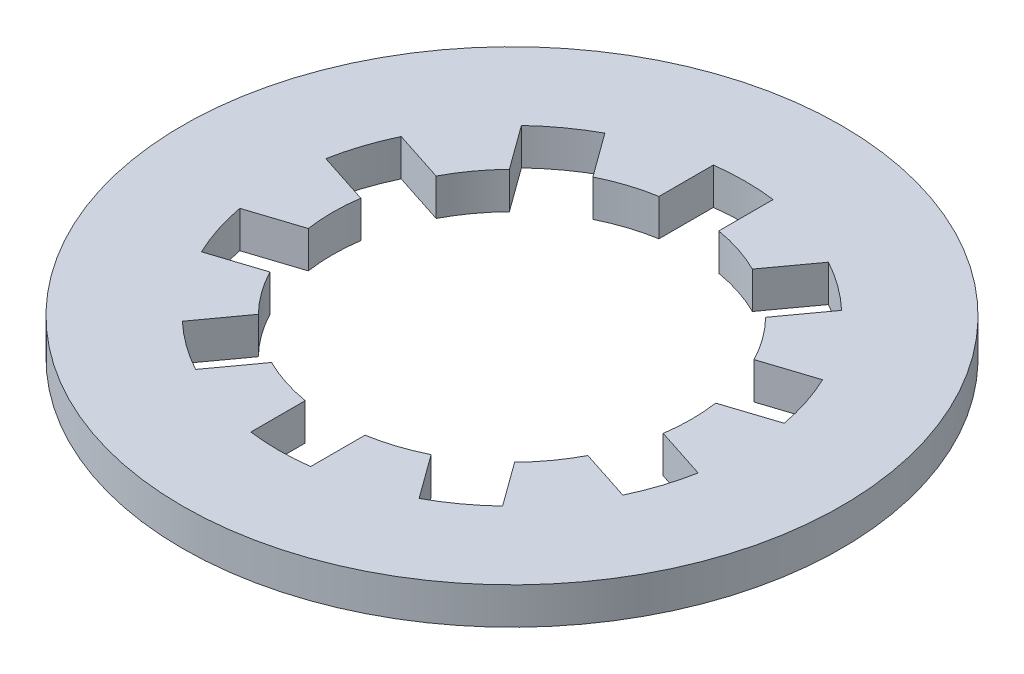
SolidWorks part; units mm, degrees
ref_plane "Front Plane" through (0, 0, 0) normal (0, 0, 1) x (1, 0, 0)
ref_plane "Top Plane" through (0, 0, 0) normal (0, 1, 0) x (1, 0, 0)
ref_plane "Right Plane" through (0, 0, 0) normal (1, 0, 0) x (0, 0, -1)
sketch "Sketch1" plane through (0, 0, 0) normal (0, 1, 0) x (1, 0, 0)
  line L0 (0, 0) -> (0, 7.5854) construction
  circle A0 centre (0, 0) radius 7.747
  circle A1 centre (0, 0) radius 4.2164
  dimension "B" = 15.494
  dimension "A" = 8.4328
extrude "Extrude1" add sketch "Sketch1" along normal blind 0.8636
sketch "Sketch2" plane through (0, 0.8636, 0) normal (0, 1, 0) x (-1, 0, 0)
  line L0 (0, 0) -> (0, 9.0768) construction
  line L3 (-0.7027, 5.4361) -> (-0.7027, 4.1574)
  line L5 (0.7027, 5.4361) -> (0.7027, 4.1574)
  circle A0 centre (0, 0) radius 4.2164 construction
  arc A1 (0.7027, 4.1574) -> (-0.7027, 4.1574) centre (0, 0) ccw
  arc A2 (0.7027, 5.4361) -> (-0.7027, 5.4361) centre (0, 0) ccw
  dimension "D1" = 5.4813
  dimension "D2" = 1.4055
extrude "Cut-Extrude1" cut sketch "Sketch2" against normal through all
ref_axis "Axis1" through (0, 7.2309, 0) along (0, -1, 0)
pattern_circular "CirPattern1" count 10 over 360 about axis through (0, 7.2309, 0) along (0, -1, 0) of "Cut-Extrude1"
pattern_circular "CirPattern2" [suppressed] count 9 over 360 about axis through (0, 7.2309, 0) along (0, -1, 0) of bodies 102
equation "\"D1@Sketch2\" = \"A@Sketch1\" * 0.65"
equation "\"D2@Sketch2\" = \"A@Sketch1\"/6"
